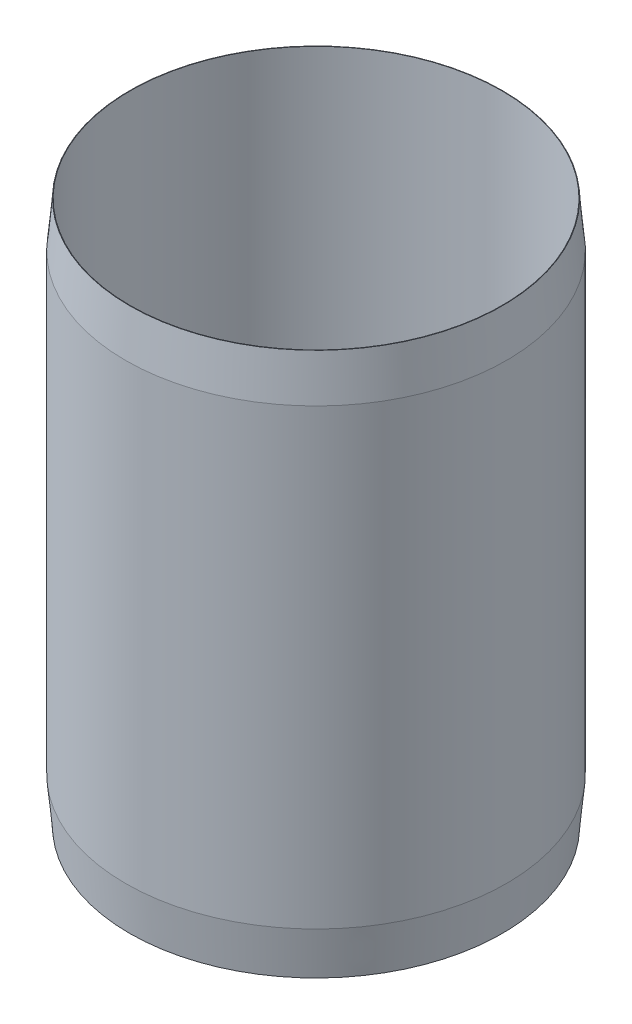
SolidWorks part; units mm, degrees
ref_plane "Front Plane" through (0, 0, 0) normal (0, 0, 1) x (1, 0, 0)
ref_plane "Top Plane" through (0, 0, 0) normal (0, 1, 0) x (1, 0, 0)
ref_plane "Right Plane" through (0, 0, 0) normal (1, 0, 0) x (0, 0, -1)
sketch "Sketch1" plane through (0, 0, 0) normal (0, 1, 0) x (1, 0, 0)
  circle A0 centre (0, 0) radius 41.05
  circle A1 centre (0, 0) radius 42.05
  dimension "D1" = 82.1
  dimension "D2" = 1
extrude "Boss-Extrude1" add sketch "Sketch1" along normal blind 120
chamfer "Chamfer1" distance 10 distance2 0.9 1 edges at (0, 120, 42.05) first distance on face at (0, 120, 42.05)
chamfer "Chamfer2" distance 0.9 distance2 10 1 edges at (0, 0, 42.05) first distance on face at (0, 0, 42.05)
